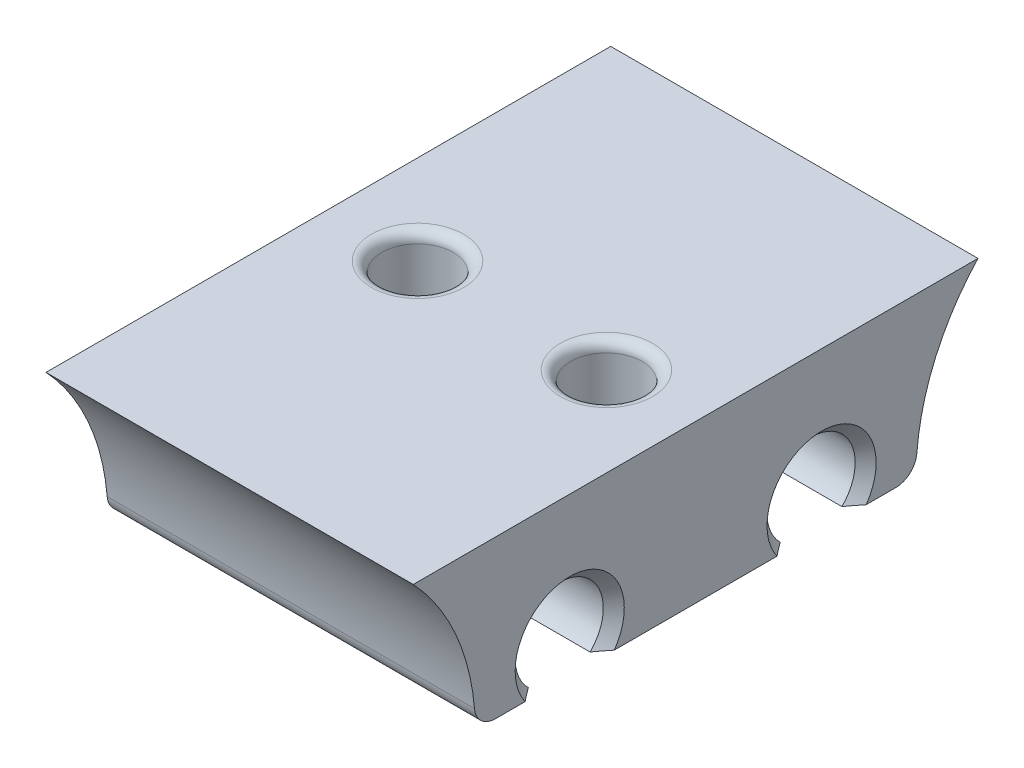
SolidWorks part; units mm, degrees
ref_plane "Front Plane" through (0, 0, 0) normal (0, 0, 1) x (1, 0, 0)
ref_plane "Top Plane" through (0, 0, 0) normal (0, 1, 0) x (1, 0, 0)
ref_plane "Right Plane" through (0, 0, 0) normal (1, 0, 0) x (0, 0, -1)
sketch "Sketch1" plane through (0, 0, 0) normal (0, 0, 1) x (1, 0, 0)
  line L0 (8.75, 4.25) -> (8.75, -1.75) construction
  line L1 (-8.75, -4.25) -> (8.75, -4.25)
  line L2 (-8.75, -4.25) -> (-8.75, 4.25)
  line L3 (-8.75, 4.25) -> (8.75, 4.25)
  line L4 (8.75, -4.25) -> (8.75, 4.25)
  line L5 (-8.75, -4.25) -> (8.75, 4.25) construction
  line L6 (-8.75, 4.25) -> (8.75, -4.25) construction
  point P0 (0, 0)
  point P6 (8.75, -4.6345)
  point P8 (8.75, -3.8937)
  dimension "D1" = 17.5
  dimension "D2" = 6
  dimension "D3" = 8.5
extrude "Boss-Extrude1" add sketch "Sketch1" along normal mid plane 21
sketch "Sketch2" plane through (-8.75, 0, 0) normal (-1, 0, 0) x (0, 0, 1)
  line L0 (0, -1.75) -> (6, -1.75) construction
  line L1 (10.5, 4.25) -> (-10.5, 4.25) construction
  line L2 (0, -1.75) -> (0, 0) construction
  line L3 (10.5, -4.25) -> (-10.5, -4.25) construction
  line L4 (3.4019, -3.25) -> (-3.4019, -3.25)
  line L5 (-4.3417, -4.25) -> (4.3417, -4.25)
  circle A0 centre (6, -1.75) radius 2.1
  circle A1 centre (-6, -1.75) radius 2.1
  arc A2 (4.3417, -4.25) -> (3.4019, -3.25) centre (6, -1.75) cw
  arc A3 (-4.3417, -4.25) -> (-3.4019, -3.25) centre (-6, -1.75) ccw
  point P17 (0, -3.25)
  dimension "D3" = 4.2
  dimension "D4" = 3
  dimension "D1" = 6
  dimension "D2" = 6
  dimension "D5" = 1.5
extrude "Cut-Extrude1" cut sketch "Sketch2" against normal through all both and the other way through all
chamfer "Chamfer1" distance 0.5 angle 45 4 edges at (8.75, -1.75, 8.1) (8.75, -1.75, -8.1) (-8.75, -1.75, 3.9) (-8.75, -1.75, -8.1)
sketch "Sketch3" plane through (0, -3.25, 0) normal (0, -1, 0) x (1, 0, 0)
  line L0 (-4.5, 0) -> (0, 0) construction
  line L1 (0, 0) -> (0, 3.4019) construction
  line L2 (8.75, 3.4019) -> (-8.75, 3.4019) construction
  circle A0 centre (-4.5, 0) radius 1.6
  circle A1 centre (4.5, 0) radius 1.6
  dimension "D1" = 3.2
  dimension "D2" = 4.5
hole_wizard "CSK for M3 Countersunk Flat Head Screw1" positions "Sketch4" profile "Sketch5" countersink size "M3" standard "ISO"
sketch "Sketch4" plane through (0, -3.25, 0) normal (0, -1, 0) x (-1, 0, 0)
  point P0 (4.5, 0)
  point P3 (-4.5, 0)
sketch "Sketch5" plane through (-4.5, -3.25, 0) normal (1, 0, 0) x (0, 0, -1)
  line L0 (0, 0) -> (0, 20.0215)
  line L1 (0, 20.0215) -> (1.7, 19)
  line L2 (1.7, 19) -> (1.7, 1.45)
  line L3 (1.7, 1.45) -> (3.15, 0)
  line L5 (3.15, 0) -> (0, 0)
  line L6 (-1.7, 1.45) -> (-3.15, 0) construction
  line L10 (0, 20.0215) -> (-1.7, 19) construction
  line L11 (0, -6.35) -> (0, 107.95) construction
  dimension "Hole Dia." = 3.4
  dimension "Hole Depth" = 19
  dimension "Near C'Sink Dia." = 6.3
  dimension "Near C'Sink Angle" = 90
  dimension "Drill Angle" = 118
fillet "Fillet1" radius 0.5 2 edges at (-4.5, 4.25, -1.7) (4.5, 4.25, -1.7)
sketch "Sketch6" plane through (-8.75, 0, 0) normal (-1, 0, 0) x (0, 0, 1)
  line L0 (-10.5, 4.25) -> (-10.5, -4.25) construction
  line L1 (-10.5, -3.25) -> (10.5, -3.25)
  line L2 (-10.5, -3.25) -> (-10.5, -4.25)
  line L3 (-10.5, -4.25) -> (10.5, -4.25)
  line L4 (10.5, -3.25) -> (10.5, -4.25)
  line L5 (-3.4019, -3.25) -> (3.4019, -3.25) construction
extrude "Cut-Extrude2" cut sketch "Sketch6" against normal through all both and the other way through all
sketch "Sketch8" plane through (-8.75, 0, 0) normal (-1, 0, 0) x (0, 0, 1)
  line L0 (10.5, 4.25) -> (-10.5, 4.25) construction
  line L1 (-13.4533, 4.25) -> (-10.5, 4.25)
  line L2 (-10.5, 4.25) -> (-10.5, -3.25)
  line L3 (0, 0) -> (0, 4.25) construction
  line L4 (13.4533, 4.25) -> (10.5, 4.25)
  line L5 (10.5, 4.25) -> (10.5, -3.25)
  arc A0 (-10.5, -3.25) -> (-13.4533, 4.25) centre (-21.5, -3.25) ccw
  arc A1 (10.5, -3.25) -> (13.4533, 4.25) centre (21.5, -3.25) cw
  dimension "D1" = 11
extrude "Boss-Extrude2" add sketch "Sketch8" against normal up to surface (17.5 mm away) up to face at (8.75, -0.35, 0)
fillet "Fillet2" radius 1 2 edges at (0, -3.25, -10.5) (0, -3.25, 10.5)
